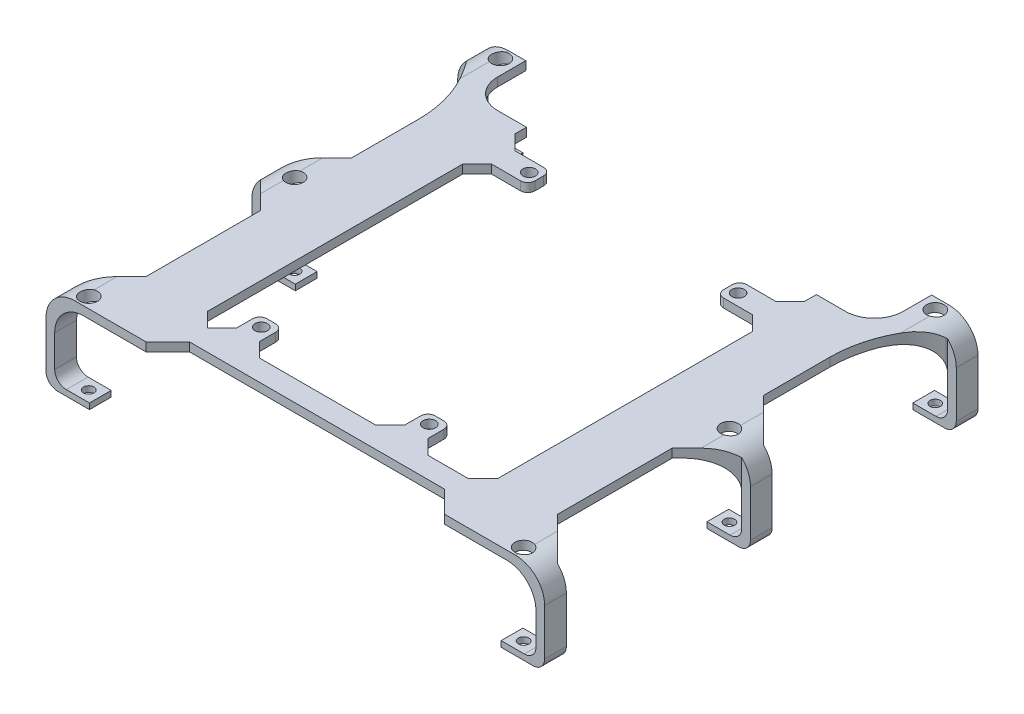
SolidWorks part; units mm, degrees
ref_plane "Alzado" through (0, 0, 0) normal (0, 0, 1) x (1, 0, 0)
ref_plane "Planta" through (0, 0, 0) normal (0, 1, 0) x (1, 0, 0)
ref_plane "Vista lateral" through (0, 0, 0) normal (1, 0, 0) x (0, 0, -1)
sketch "Croquis1" plane through (0, 0, 0) normal (0, 1, 0) x (1, 0, 0)
  line L0 (-75, 0) -> (75, 0) construction
  line L1 (0, 71) -> (0, -71) construction
  line L2 (-75, 71) -> (75, 71) construction
  line L3 (-75, -71) -> (75, -71) construction
  line L4 (-71, 71) -> (-71, 74.75)
  line L5 (-71, 74.75) -> (-86, 74.75)
  line L6 (-86, 74.75) -> (-86, 67.25)
  line L7 (-86, 67.25) -> (-71, 67.25)
  line L8 (-71, 67.25) -> (-71, 71)
  line L9 (-86, -67.25) -> (-71, -67.25)
  line L10 (-86, -74.75) -> (-86, -67.25)
  line L11 (-71, -74.75) -> (-86, -74.75)
  line L12 (-71, -71) -> (-71, -74.75)
  line L13 (-71, -67.25) -> (-71, -71)
  line L14 (-71, 0) -> (-71, 3.75)
  line L15 (-71, 3.75) -> (-86, 3.75)
  line L16 (-86, 3.75) -> (-86, -3.75)
  line L17 (-86, -3.75) -> (-71, -3.75)
  line L18 (-71, -3.75) -> (-71, 0)
  line L19 (86, -74.75) -> (86, -67.25)
  line L20 (71, -74.75) -> (86, -74.75)
  line L21 (71, -71) -> (71, -74.75)
  line L22 (71, -67.25) -> (71, -71)
  line L23 (86, -67.25) -> (71, -67.25)
  line L24 (86, -3.75) -> (71, -3.75)
  line L25 (86, 3.75) -> (86, -3.75)
  line L26 (71, 3.75) -> (86, 3.75)
  line L27 (71, 0) -> (71, 3.75)
  line L28 (71, -3.75) -> (71, 0)
  line L29 (86, 67.25) -> (71, 67.25)
  line L30 (86, 74.75) -> (86, 67.25)
  line L31 (71, 74.75) -> (86, 74.75)
  line L32 (71, 71) -> (71, 74.75)
  line L33 (71, 67.25) -> (71, 71)
  circle A0 centre (-75, 71) radius 1.8
  circle A1 centre (-75, 0) radius 1.8
  circle A2 centre (-75, -71) radius 1.8
  circle A3 centre (75, -71) radius 1.8
  circle A4 centre (75, 0) radius 1.8
  circle A5 centre (75, 71) radius 1.8
  point P4 (0, 0)
  point P8 (0, 0)
  point P10 (0, 71)
  point P13 (0, -71)
  dimension "D4" = 3.6
  dimension "D1" = 71
  dimension "D2" = 71
  dimension "D3" = 150
  dimension "D5" = 7.5
  dimension "D6" = 4
  dimension "D7" = 15
extrude "Saliente-Extruir1" add sketch "Croquis1" along normal blind 2
sketch "Croquis2" plane through (0, 2, 0) normal (0, 1, 0) x (1, 0, 0)
  line L0 (-86, 74.75) -> (-86, 67.25)
  line L1 (-86, 67.25) -> (-83, 67.25)
  line L2 (-86, 67.25) -> (-71, 67.25) construction
  line L3 (-83, 67.25) -> (-83, 74.75)
  line L4 (-71, 74.75) -> (-86, 74.75) construction
  line L5 (-83, 74.75) -> (-86, 74.75)
  line L6 (-86, 3.75) -> (-83, 3.75)
  line L7 (-71, 3.75) -> (-86, 3.75) construction
  line L8 (-83, 3.75) -> (-83, -3.75)
  line L9 (-86, -3.75) -> (-71, -3.75) construction
  line L10 (-83, -3.75) -> (-86, -3.75)
  line L11 (-86, -3.75) -> (-86, 3.75)
  line L12 (-19.9225, 0) -> (0, 0) construction
  line L13 (0, 0) -> (0, 24.6501) construction
  line L14 (-83, -67.25) -> (-83, -74.75)
  line L15 (-86, -67.25) -> (-83, -67.25)
  line L16 (-86, -74.75) -> (-86, -67.25)
  line L17 (-83, -74.75) -> (-86, -74.75)
  line L18 (86, -67.25) -> (83, -67.25)
  line L19 (86, -74.75) -> (86, -67.25)
  line L20 (83, -74.75) -> (86, -74.75)
  line L21 (83, -67.25) -> (83, -74.75)
  line L22 (83, -3.75) -> (86, -3.75)
  line L23 (83, 3.75) -> (83, -3.75)
  line L24 (86, 3.75) -> (83, 3.75)
  line L25 (86, -3.75) -> (86, 3.75)
  line L26 (83, 67.25) -> (83, 74.75)
  line L27 (86, 67.25) -> (83, 67.25)
  line L28 (86, 74.75) -> (86, 67.25)
  line L29 (83, 74.75) -> (86, 74.75)
  dimension "D1" = 3
extrude "Saliente-Extruir2" add sketch "Croquis2" along normal blind 25
sketch "Croquis3" plane through (0, 27, 0) normal (0, 1, 0) x (1, 0, 0)
  line L0 (-86, 74.75) -> (-56, 74.75)
  line L4 (-86, 67.25) -> (-71, 67.25)
  line L5 (-71, 67.25) -> (-71, 3.75)
  line L6 (-71, 3.75) -> (-86, 3.75)
  line L7 (-86, 67.25) -> (-86, 74.75)
  line L8 (-86, 3.75) -> (-86, -3.75)
  line L9 (-86, -3.75) -> (-71, -3.75)
  line L10 (-71, -3.75) -> (-71, -67.25)
  line L11 (-71, -67.25) -> (-86, -67.25)
  line L12 (-86, -67.25) -> (-86, -74.75)
  line L13 (-86, -74.75) -> (-56, -74.75)
  line L14 (86, -74.75) -> (86, -67.25) construction
  line L15 (86, -74.75) -> (86, -67.25)
  line L16 (86, -67.25) -> (71, -67.25)
  line L17 (71, -67.25) -> (71, -3.75)
  line L18 (71, -3.75) -> (86, -3.75)
  line L19 (86, -3.75) -> (86, 3.75)
  line L20 (86, -3.75) -> (86, 3.75) construction
  line L21 (86, 3.75) -> (71, 3.75)
  line L22 (71, 3.75) -> (71, -3.75) construction
  line L23 (71, 3.75) -> (71, 67.25)
  line L24 (71, 67.25) -> (86, 67.25)
  line L25 (86, 67.25) -> (86, 74.75)
  line L26 (-56, 74.75) -> (-56, 67.25)
  line L27 (-56, 67.25) -> (56, 67.25)
  line L28 (56, 67.25) -> (56, 74.75)
  line L29 (-56, -74.75) -> (-56, -67.25)
  line L30 (-56, -67.25) -> (56, -67.25)
  line L31 (56, -67.25) -> (56, -74.75)
  line L32 (56, 74.75) -> (86, 74.75)
  line L33 (56, -74.75) -> (86, -74.75)
  dimension "D1" = 15
extrude "Saliente-Extruir3" add sketch "Croquis3" along normal blind 3
chamfer "Chaflán2" distance 12 angle 45 8 edges at (71, 28.5, -67.25) (71, 28.5, 3.75) (71, 28.5, -3.75) (71, 28.5, 67.25) (-71, 28.5, 67.25) (-71, 28.5, -3.75) (-71, 28.5, -67.25) (-71, 28.5, 3.75)
fillet "Redondeo1" radius 10 12 edges at (86, 30, 0) (86, 30, -71) (-86, 30, -71) (83, 27, -71) (-86, 30, 0) (83, 27, 0) (-86, 30, 71) (83, 27, 71) (86, 30, 71) (-83, 27, -71) (-83, 27, 0) (-83, 27, 71)
fillet "Redondeo2" radius 4 12 edges at (86, 0, -71) (83, 2, -71) (83, 2, 0) (86, 0, 0) (-86, 0, -71) (-83, 2, -71) (-86, 0, 0) (-83, 2, 0) (86, 0, 71) (83, 2, 71) (-86, 0, 71) (-83, 2, 71)
chamfer "Chaflán3" distance 12 angle 45 4 edges at (56, 28.5, 67.25) (-56, 28.5, 67.25) (-56, 28.5, -67.25) (56, 28.5, -67.25)
sketch "Croquis4" plane through (0, 27, 0) normal (0, -1, 0) x (1, 0, 0)
  line L0 (0, 0) -> (0, 60) construction
  line L1 (-35.0593, 0) -> (0, 0) construction
  line L2 (0, 60) -> (50, 60)
  line L3 (50, 60) -> (50, -55)
  line L5 (-50, -55) -> (-50, 60)
  line L6 (-50, 60) -> (0, 60)
  line L7 (0, 0) -> (0, -55) construction
  line L8 (-50, -55) -> (-70, -55)
  line L9 (-70, -55) -> (-70, -85)
  line L10 (-70, -85) -> (70, -85)
  line L11 (70, -85) -> (70, -55)
  line L12 (70, -55) -> (50, -55)
  circle A0 centre (-75, 71) radius 3
  circle A1 centre (-75, 0) radius 3
  circle A2 centre (-75, -71) radius 3
  circle A3 centre (75, -71) radius 3
  circle A4 centre (75, 0) radius 3
  circle A5 centre (75, 71) radius 3
  dimension "D1" = 6
  dimension "D2" = 30
  dimension "D3" = 100
  dimension "D4" = 55
  dimension "D5" = 20
  dimension "D6" = 60
extrude "Cortar-Extruir1" cut sketch "Croquis4" against normal through all and the other way blind 3
fillet "Redondeo3" radius 40 2 edges at (-71, 28.5, -55.25) (71, 28.5, -55.25)
fillet "Redondeo4" radius 10 2 edges at (-70, 28.5, -55) (70, 28.5, -55)
sketch "Croquis5" plane through (0, 30, 0) normal (0, 1, 0) x (1, 0, 0)
  line L0 (25.975, -60) -> (25.975, -46.9873)
  line L1 (50, -60) -> (-50, -60) construction
  line L2 (25.975, -46.9873) -> (17.975, -46.9873)
  line L3 (17.975, -46.9873) -> (17.975, -60)
  line L4 (17.975, -60) -> (25.975, -60)
  line L5 (-32.025, -60) -> (-32.025, -46.9873)
  line L6 (-32.025, -46.9873) -> (-40.025, -46.9873)
  line L7 (-40.025, -46.9873) -> (-40.025, -60)
  line L8 (-40.025, -60) -> (-32.025, -60)
  line L9 (-50, 45.9627) -> (-32.525, 45.9627)
  line L10 (-50, -60) -> (-50, 55) construction
  line L11 (-32.525, 45.9627) -> (-32.525, 37.9627)
  line L12 (-32.525, 37.9627) -> (-50, 37.9627)
  line L13 (-50, 37.9627) -> (-50, 45.9627)
  line L14 (50, 45.9627) -> (32.525, 45.9627)
  line L15 (50, 55) -> (50, -60) construction
  line L17 (32.525, 45.9627) -> (32.525, 37.9627)
  line L18 (32.525, 37.9627) -> (50, 37.9627)
  line L19 (50, 37.9627) -> (50, 45.9627)
  line L20 (-50, 41.9627) -> (-36.025, 41.9627) construction
  line L21 (-36.025, 41.9627) -> (-32.525, 41.9627) construction
  line L22 (32.525, 41.9627) -> (36.025, 41.9627) construction
  line L23 (36.025, 41.9627) -> (50, 41.9627) construction
  line L24 (-36.025, -46.9873) -> (-36.025, -50.4873) construction
  line L25 (-36.025, -50.4873) -> (-36.025, -60) construction
  line L26 (21.975, -46.9873) -> (21.975, -50.4873) construction
  line L27 (21.975, -50.4873) -> (21.975, -60) construction
  line L28 (-36.025, 41.9627) -> (0, 41.9627) construction
  line L29 (0, 41.9627) -> (36.025, 41.9627) construction
  line L30 (0, 0) -> (0, 41.9627) construction
  arc A0 (50.1934, 37.5215) -> (48.9934, 37.5215) centre (49.5934, 37.5215) ccw construction
  circle A1 centre (-36.025, 41.9627) radius 2.15
  circle A2 centre (36.025, 41.9627) radius 2.15
  circle A3 centre (21.975, -50.4873) radius 2.15
  circle A4 centre (-36.025, -50.4873) radius 2.15
  dimension "D2" = 4.3
  dimension "D1" = 3.5
  dimension "D3" = 8
  dimension "D4" = 72.05
  dimension "D5" = 92.45
  dimension "D6" = 58
extrude "Saliente-Extruir4" add sketch "Croquis5" against normal blind 3
chamfer "Chaflán4" distance 5 angle 45 10 edges at (-50, 28.5, 60) (50, 28.5, 60) (50, 28.5, -45.9627) (50, 28.5, -37.9627) (17.975, 28.5, 60) (25.975, 28.5, 60) (-40.025, 28.5, 60) (-32.025, 28.5, 60) (-50, 28.5, -37.9627) (-50, 28.5, -45.9627)
fillet "Redondeo5" radius 2.5 8 edges at (32.525, 28.5, -37.9627) (32.525, 28.5, -45.9627) (-32.525, 28.5, -37.9627) (-32.525, 28.5, -45.9627) (-40.025, 28.5, 46.9873) (-32.025, 28.5, 46.9873) (17.975, 28.5, 46.9873) (25.975, 28.5, 46.9873)
